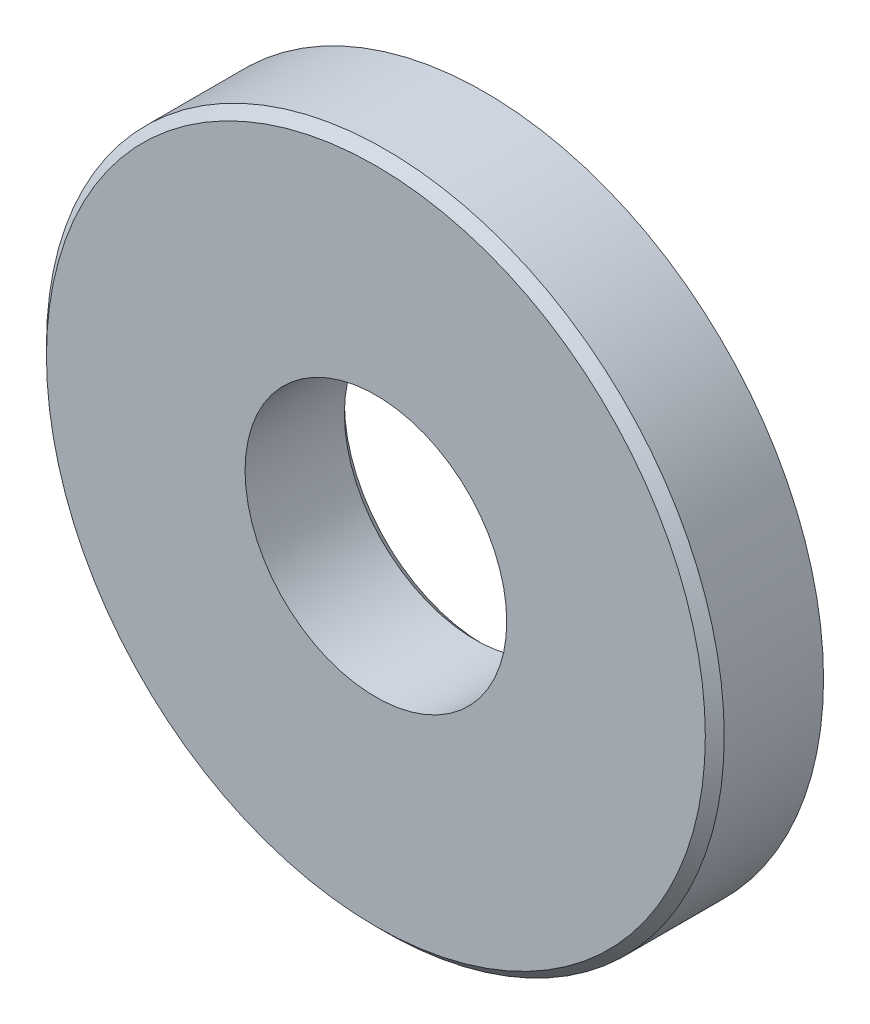
SolidWorks part; units mm, degrees
ref_plane "前视基准面" through (0, 0, 0) normal (0, 0, 1) x (1, 0, 0)
ref_plane "上视基准面" through (0, 0, 0) normal (0, 1, 0) x (1, 0, 0)
ref_plane "右视基准面" through (0, 0, 0) normal (1, 0, 0) x (0, 0, -1)
sketch "草图1" plane through (0, 0, 0) normal (0, 0, 1) x (1, 0, 0)
  circle A0 centre (0, 0) radius 4.15
  circle A1 centre (0, 0) radius 10.75
extrude "凸台-拉伸1" add sketch "草图1" along normal blind 3.45
chamfer "倒角1" distance 0.3 angle 45 1 edges at (10.75, 0, 3.45)
chamfer "倒角2" distance 0.3 angle 45 1 edges at (4.15, 0, 0)
